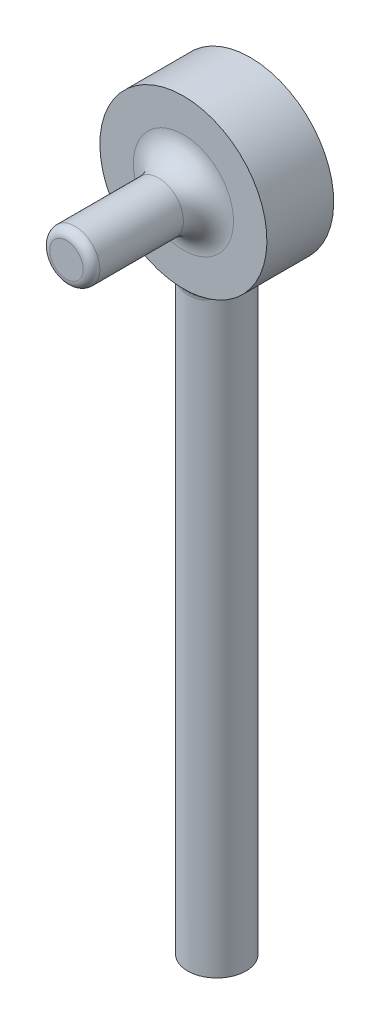
SolidWorks part; units mm, degrees
material "PLA-custom"
ref_plane "Front Plane" through (0, 0, 0) normal (0, 0, 1) x (1, 0, 0)
ref_plane "Top Plane" through (0, 0, 0) normal (0, 1, 0) x (1, 0, 0)
ref_plane "Right Plane" through (0, 0, 0) normal (1, 0, 0) x (0, 0, -1)
sketch "Sketch1" plane through (0, 0, 0) normal (0, 1, 0) x (1, 0, 0)
  circle A0 centre (0, 0) radius 3.5
extrude "Boss-Extrude1" add sketch "Sketch1" along normal blind 90
sketch "Sketch4" plane through (0, 0, 0) normal (0, 0, 1) x (1, 0, 0)
  circle A1 centre (0, 9) radius 10
extrude "Boss-Extrude2" add sketch "Sketch4" along normal blind 4
extrude "Boss-Extrude3" add sketch "Sketch4<7>" against normal blind 4
sketch "Sketch4<7>" plane through (0, 0, 0) normal (0, 0, 1) x (1, 0, 0) same geometry as "Sketch4"
sketch "Sketch5" plane through (0, 0, 4) normal (0, 0, 1) x (1, 0, 0)
  circle A0 centre (0, 9) radius 3
  dimension "D1" = 6
extrude "Boss-Extrude4" add sketch "Sketch5" along normal blind 14
fillet "Fillet1" radius 3 1 edges at (3, 9, 4)
fillet "Fillet2" radius 1 1 edges at (3, 9, 18)
fillet "Fillet3" radius 1 1 edges at (-3.5, 18.3675, 0)
move or copy body "Body-Move/Copy2" bodies to move or copy 112 copy no translate (0, -9, 0) parameters "D1"=0, "D2"=9, "D3"=0
move or copy body "Body-Move/Copy4" bodies to move or copy 114 copy no rotation origin (0, 0, 0) rotation axis (0, 0, 1) rotation angle 180
